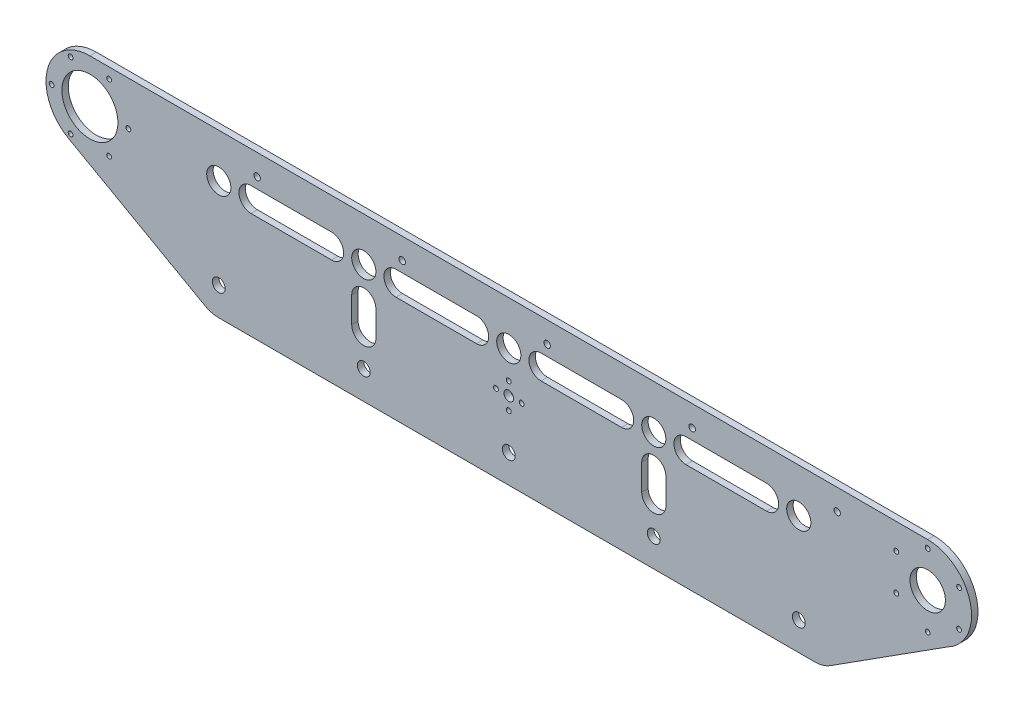
SolidWorks part; units mm, degrees
material "3.1305 (EN-AW 2117)"
ref_plane "Alzado" through (0, 0, 0) normal (0, 0, 1) x (1, 0, 0)
ref_plane "Planta" through (0, 0, 0) normal (0, 1, 0) x (1, 0, 0)
ref_plane "Vista lateral" through (0, 0, 0) normal (1, 0, 0) x (0, 0, -1)
sketch "Croquis1" plane through (0, 0, 0) normal (0, 0, 1) x (1, 0, 0)
  line L4 (102.5, 23.182) -> (90, 21.1607) construction
  line L5 (90, -23.8925) -> (180, -23.8925) construction
  line L6 (-102.5, -9.9669) -> (-83.0991, -6.8298) construction
  line L7 (-215.9366, -23.8925) -> (-260, -23.8925) construction
  line L8 (-90, -23.8925) -> (-94, -23.8925) construction
  line L9 (-188.6184, -23.8925) -> (-184, -23.8925) construction
  line L10 (-260, -23.8925) -> (-260, 1.2874) construction
  line L11 (-179.1956, -41.4802) -> (179.1956, -41.4802)
  line L12 (-260, 32.1075) -> (-180, -23.8925) construction
  line L18 (179.1956, -41.4802) -> (190.0108, -41.4802)
  line L19 (0, -23.8925) -> (-12.5, -23.8925) construction
  line L20 (-180, -23.8925) -> (-167.5, -23.8925) construction
  line L21 (-90, -23.8925) -> (-94, -23.8925) construction
  line L24 (-90, -23.8925) -> (-90, 32.1075) construction
  line L28 (-183.9999, -23.9199) -> (-188.6184, -23.8925) construction
  line L30 (-180, -23.8925) -> (-196.3846, -12.4232) construction
  line L31 (-196.3846, -12.4232) -> (-221.6689, 5.2758) construction
  line L32 (-260, 32.1075) -> (-243.6154, 20.6383) construction
  line L36 (-272.7427, 8.0318) -> (-188.6256, -39.2409)
  line L41 (-90, 32.1075) -> (-90, 12.1075) construction
  line L42 (-90, -23.8925) -> (-90, -3.8925) construction
  line L43 (-82.5, 12.1075) -> (-82.5, -3.8925)
  line L44 (-97.5, 12.1075) -> (-97.5, -3.8925)
  line L45 (-90, 44.6075) -> (-90, -11.3925) construction
  line L46 (-20, 24.6075) -> (-70, 24.6075)
  line L47 (-20, 39.6075) -> (-70, 39.6075)
  line L48 (287.24, 32.1075) -> (284.0739, 32.1075) construction
  line L50 (260, 59.3475) -> (260, 32.1075) construction
  line L51 (90, 44.6075) -> (90, -11.3925) construction
  line L52 (90, -23.8925) -> (90, -3.8925) construction
  line L53 (90, 32.1075) -> (90, 12.1075) construction
  line L54 (260, 32.1075) -> (260, 39.1075) construction
  line L56 (-260, 4.1) -> (-260, 32.1075) construction
  line L59 (20, 39.6075) -> (70, 39.6075)
  line L60 (260, 32.1075) -> (260, 25.1075) construction
  line L65 (-160, 39.6075) -> (-110, 39.6075)
  line L66 (-160, 24.6075) -> (-110, 24.6075)
  line L83 (-260, 59.3475) -> (260, 59.3475)
  line L87 (-287.24, 32.1075) -> (-284.0739, 32.1075) construction
  line L89 (160, 24.6075) -> (110, 24.6075)
  line L91 (-167.5, -23.8925) -> (-180, -23.8925) construction
  line L92 (-102.5, 23.182) -> (-90, 21.1607) construction
  line L93 (160, 39.6075) -> (110, 39.6075)
  line L94 (-6.5, 6.6075) -> (-141.7981, 6.6075) construction
  line L95 (90, -23.8925) -> (86, -23.8925) construction
  line L96 (-135, 39.6075) -> (-135, 14.7545) construction
  line L97 (135, 39.6075) -> (135, 20.6383) construction
  line L98 (-86, -23.8925) -> (-90, -23.8925) construction
  line L100 (-83.0991, -6.8298) -> (-102.5, -9.9669) construction
  line L101 (-90, 21.1607) -> (-102.5, 23.182) construction
  line L103 (83.0991, -6.8298) -> (102.5, -9.9669) construction
  line L106 (90, 21.1607) -> (102.5, 23.182) construction
  line L115 (90, -23.8925) -> (90, 32.1075) construction
  line L116 (90, -23.8925) -> (94, -23.8925) construction
  line L119 (265.4417, 3.373) -> (265.4184, 3.7892) construction
  line L121 (90, -23.8925) -> (94, -23.8925) construction
  line L122 (102.5, -9.9669) -> (83.0991, -6.8298) construction
  line L124 (20, 24.6075) -> (70, 24.6075)
  line L125 (97.5, 12.1075) -> (97.5, -3.8925)
  line L126 (82.5, 12.1075) -> (82.5, -3.8925)
  line L127 (272.7427, 8.0318) -> (199.4836, -38.7153)
  circle A5 centre (0, -23.8925) radius 4
  circle A6 centre (-90, -23.8925) radius 4
  circle A7 centre (-180, -23.8925) radius 4
  circle A25 centre (-90, 32.1075) radius 7.5
  arc A26 (-82.5, 12.1075) -> (-97.5, 12.1075) centre (-90, 12.1075) ccw
  arc A27 (-97.5, -3.8925) -> (-82.5, -3.8925) centre (-90, -3.8925) ccw
  arc A28 (-20, 39.6075) -> (-20, 24.6075) centre (-20, 32.1075) cw
  arc A29 (-70, 24.6075) -> (-70, 39.6075) centre (-70, 32.1075) cw
  circle A30 centre (0, 32.1075) radius 7.5
  circle A51 centre (-260, 32.1075) radius 17.4
  arc A52 (-260, 59.3475) -> (-272.7427, 8.0318) centre (-260, 32.1075) ccw
  arc A54 (-188.6256, -39.2409) -> (-179.1956, -41.4802) centre (-180, -23.8925) ccw
  arc A56 (260, 59.3475) -> (272.7427, 8.0318) centre (260, 32.1075) cw
  circle A57 centre (260, 32.1075) radius 11
  arc A58 (70, 24.6075) -> (70, 39.6075) centre (70, 32.1075) ccw
  arc A59 (20, 39.6075) -> (20, 24.6075) centre (20, 32.1075) ccw
  arc A60 (97.5, -3.8925) -> (82.5, -3.8925) centre (90, -3.8925) cw
  arc A61 (82.5, 12.1075) -> (97.5, 12.1075) centre (90, 12.1075) cw
  circle A62 centre (90, 32.1075) radius 7.5
  circle A66 centre (90, -23.8925) radius 4
  arc A71 (-160, 39.6075) -> (-160, 24.6075) centre (-160, 32.1075) ccw
  arc A72 (-110, 24.6075) -> (-110, 39.6075) centre (-110, 32.1075) ccw
  arc A73 (160, 39.6075) -> (160, 24.6075) centre (160, 32.1075) cw
  arc A74 (110, 24.6075) -> (110, 39.6075) centre (110, 32.1075) cw
  circle A75 centre (-180, 32.1075) radius 7.5
  circle A76 centre (180, 32.1075) radius 7.5
  circle A77 centre (-8, 6.6075) radius 1.5
  circle A78 centre (0, 14.6075) radius 1.5
  circle A79 centre (8, 6.6075) radius 1.5
  circle A80 centre (0, -1.3925) radius 1.5
  circle A81 centre (0, 6.6075) radius 3
  circle A82 centre (180, -23.8925) radius 4
  arc A83 (199.4836, -38.7153) -> (190.0108, -41.4802) centre (190.0108, -23.8702) cw
  point P0 (0, 6.6075)
  dimension "D5" = 8
  dimension "D7" = 8
  dimension "D9" = 8
  dimension "D11" = 22
  dimension "D10" = 54.48
  dimension "D12" = 27.24
  dimension "D15" = 7
  dimension "D16" = 7
  dimension "D18" = 4
  dimension "D20" = 6
  dimension "D21" = 34.8
  dimension "D23" = 8
  dimension "D24" = 90
  dimension "D25" = 15
  dimension "D28" = 15
  dimension "D30" = 15
  dimension "D31" = 15
  dimension "D33" = 17.61
  dimension "D17" = 3
  dimension "D32" = 8
  dimension "D4" = 30.5
  dimension "D6" = 90
  dimension "D8" = 90
  dimension "D13" = 80
  dimension "D14" = 56
  dimension "D19" = 20
  dimension "D22" = 20
  dimension "D26" = 20
  dimension "D27" = 56
  dimension "D29" = 20
extrude "Saliente-Extruir1" add sketch "Croquis1" along normal mid plane 4
sketch "Croquis2" plane through (0, 0, 2) normal (0, 0, 1) x (1, 0, 0)
  line L0 (-287.24, 32.1075) -> (-283.74, 32.1075) construction
  line L1 (-260, 32.1075) -> (-271.95, 52.8055) construction
  line L2 (-260, 32.1075) -> (-248.05, 52.8055) construction
  line L3 (-260, 32.1075) -> (-271.95, 11.4095) construction
  line L4 (-260, 32.1075) -> (-248.05, 11.4095) construction
  line L5 (-260, 32.1075) -> (-236.1, 32.1075) construction
  line L6 (-260, 32.1075) -> (-283.74, 32.1075) construction
  arc A0 (-260, 59.3475) -> (-272.7427, 8.0318) centre (-260, 32.1075) ccw construction
  circle A1 centre (-283.74, 32.1075) radius 1.5
  circle A3 centre (-271.95, 52.8055) radius 1.5
  circle A4 centre (-248.05, 52.8055) radius 1.5
  circle A5 centre (-236.1, 32.1075) radius 1.5
  circle A6 centre (-248.05, 11.4095) radius 1.5
  circle A7 centre (-271.95, 11.4095) radius 1.5
  dimension "D2" = 3
  dimension "D12" = 3
  dimension "D13" = 3
  dimension "D14" = 3
  dimension "D15" = 3
  dimension "D16" = 3
  dimension "D1" = 3.5
  dimension "D3" = 60
  dimension "D4" = 60
  dimension "D5" = 60
  dimension "D6" = 60
  dimension "D7" = 23.9
  dimension "D8" = 23.9
  dimension "D9" = 23.9
  dimension "D10" = 23.9
  dimension "D11" = 23.9
extrude "Cortar-Extruir1" cut sketch "Croquis2" against normal blind 10
sketch "Croquis3" plane through (0, 0, 2) normal (0, 0, 1) x (1, 0, 0)
  line L0 (260, 32.1075) -> (260, 54.6075) construction
  circle A0 centre (260, 54.6075) radius 1.5
  circle A1 centre (279.4856, 43.3575) radius 1.5
  circle A2 centre (279.4856, 20.8575) radius 1.5
  circle A3 centre (260, 9.6075) radius 1.5
  circle A4 centre (240.5144, 20.8575) radius 1.5
  circle A5 centre (240.5144, 43.3575) radius 1.5
  dimension "D2" = 3
  dimension "D1" = 22.5
  dimension "D3" = 6
extrude "Cortar-Extruir2" cut sketch "Croquis3" against normal blind 10
sketch "Croquis4" plane through (0, 0, 2) normal (0, 0, 1) x (1, 0, 0)
  line L0 (240.5144, 43.3575) -> (240.5144, 46.2175) construction
  line L1 (-156.1656, 44.2175) -> (-156.1656, 46.2175) construction
  line L2 (-156.1656, 46.2175) -> (-66.1656, 46.2175) construction
  line L3 (-66.1656, 46.2175) -> (23.8344, 46.2175) construction
  line L4 (23.8344, 46.2175) -> (113.8344, 46.2175) construction
  line L5 (113.8344, 46.2175) -> (203.8344, 46.2175) construction
  line L6 (240.5144, 46.2175) -> (203.8344, 46.2175) construction
  circle A0 centre (-156.1656, 46.2175) radius 2
  circle A1 centre (-66.1656, 46.2175) radius 2
  circle A2 centre (23.8344, 46.2175) radius 2
  circle A3 centre (113.8344, 46.2175) radius 2
  circle A4 centre (203.8344, 46.2175) radius 2
  dimension "D3" = 4
  dimension "D8" = 4
  dimension "D9" = 4
  dimension "D10" = 4
  dimension "D11" = 4
  dimension "D2" = 2.86
  dimension "D4" = 90
  dimension "D5" = 90
  dimension "D6" = 90
  dimension "D7" = 90
  dimension "D12" = 36.68
extrude "Cortar-Extruir3" cut sketch "Croquis4" against normal blind 10
